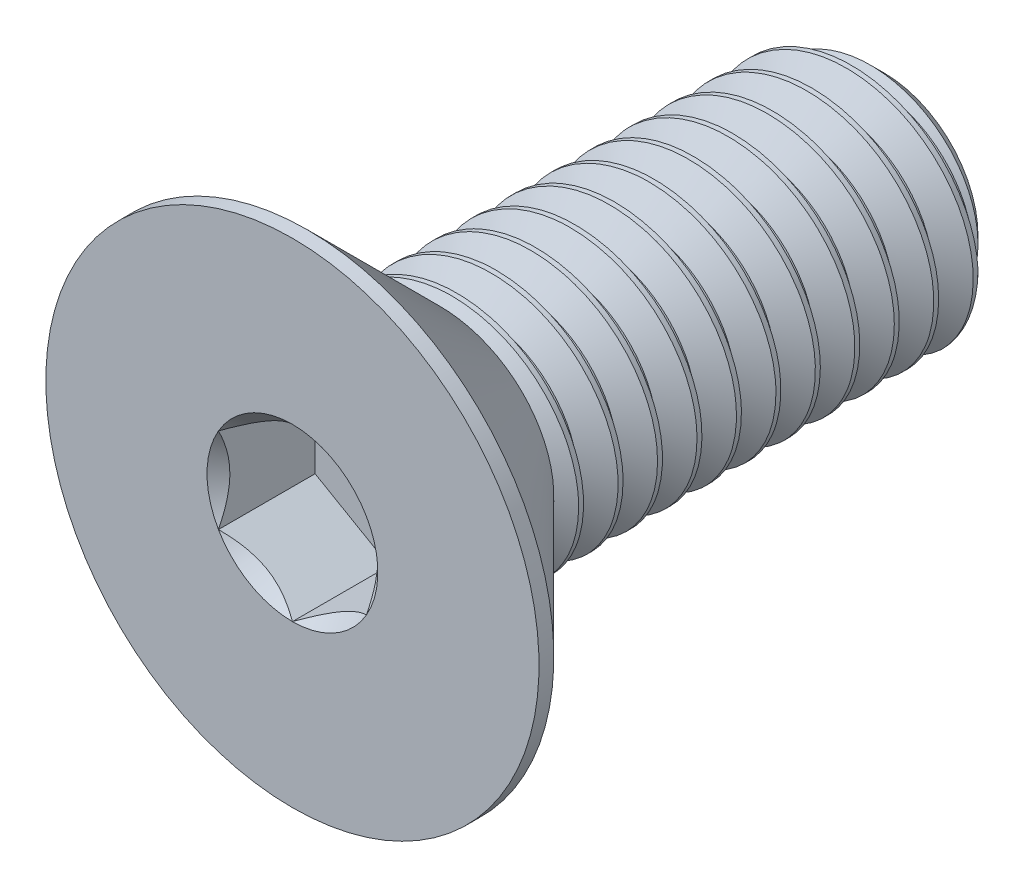
SolidWorks part; units mm, degrees
ref_plane "Front" through (0, 0, 0) normal (0, 0, 1) x (1, 0, 0)
ref_plane "Top" through (0, 0, 0) normal (0, 1, 0) x (1, 0, 0)
ref_plane "Right" through (0, 0, 0) normal (1, 0, 0) x (0, 0, -1)
sketch "Body Sketch" plane through (0, 0, 0) normal (1, 0, 0) x (0, 0, -1)
  line L0 (0, 5) -> (0.3, 5) construction
  line L1 (0.3, 5) -> (2.8, 2.5) construction
  line L2 (0, 2.5) -> (12, 2.5)
  line L3 (12, 2.5) -> (12, 0)
  line L4 (12, 0) -> (0, 0)
  line L5 (0, 0) -> (0, 5) construction
  line L6 (0, 5) -> (0, -5) construction
  line L7 (12, 2.5) -> (12, -2.5) construction
  line L8 (0, -5) -> (0.3, -5) construction
  line L9 (0.3, -5) -> (2.8, -2.5) construction
  line L11 (0, 2.5) -> (0, 0)
  line L12 (2.8, 2.5) -> (2.8, 0) construction
revolve "Body Revolve" add sketch "Body Sketch" angle 360 mid plane about L4
sketch "Sketch3" plane through (0, 0, -12) normal (0, 0, -1) x (-1, 0, 0)
  circle A0 centre (0, 0) radius 2.5
curve "Helix/Spiral1" pitch 0.8 height 12 radius 2.5 centre (0, 0, -12) axis (0, 0, 1) start towards (0, 1, 0)
sketch "Sketch2" plane through (0, 0, 0) normal (1, 0, 0) x (0, 0, -1)
  line L0 (12, 2.5) -> (12.7, 2.5)
  line L1 (12.7, 2.5) -> (12.4, 1.9804)
  line L2 (12.4, 1.9804) -> (12.3, 1.9804)
  line L3 (12.3, 1.9804) -> (12, 2.5)
  line L4 (12.15, 2.2402) -> (12.55, 2.2402) construction
  dimension "D1" = 60
  dimension "D2" = 0.1
  dimension "D3" = 0.4
chamfer "Chamfer1" distance 0.6 angle 45 1 edges at (0, 2.5, -12)
sweep "Cut-Sweep1" cut profiles "Sketch2" path "Helix/Spiral1" align with end faces yes
sketch "Sketch7" plane through (0, 0, 0) normal (1, 0, 0) x (0, 0, -1)
  line L0 (0, 5) -> (0.3, 5) construction
  line L1 (0.3, 5) -> (2.8, 2.5) construction
  line L2 (0, 5) -> (0.3, 5)
  line L3 (0.3, 5) -> (2.8, 2.5)
  line L4 (2.8, 2.5) -> (2.8, 0) construction
  line L5 (2.8, 2.5) -> (2.8, 0)
  line L7 (0, 0) -> (0, 5) construction
  line L8 (0, 0) -> (0, 5)
  line L9 (0, 0) -> (2.8, 0)
  line L10 (5.5, 0) -> (-5.5, 0) construction
revolve "Revolve2" add sketch "Sketch7" angle 360 mid plane about L9
ref_plane "Plane1" through (0, 0, -2.8) normal (0, 0, 1) x (1, 0, 0)
sketch "Sketch8" plane through (0, 0, -2.8) normal (0, 0, 1) x (1, 0, 0)
  circle A0 centre (0, 0) radius 2.5
extrude "Boss-Extrude1" add sketch "Sketch8" against normal through all draft 45
sketch "Sketch5" plane through (0, 0, 0) normal (0, 0, 1) x (1, 0, 0)
  line L1 (1.5, -0.866) -> (1.5, 0.866)
  line L2 (1.5, 0.866) -> (0, 1.7321)
  line L3 (0, 1.7321) -> (-1.5, 0.866)
  line L4 (-1.5, 0.866) -> (-1.5, -0.866)
  line L5 (-1.5, -0.866) -> (0, -1.7321)
  line L6 (0, -1.7321) -> (1.5, -0.866)
  circle A0 centre (0, 0) radius 1.5 construction
  dimension "Hex" = 3
extrude "Cut-Extrude2" cut sketch "Sketch5" against normal blind 1.96
sketch "Sketch6" plane through (0, 0, 0) normal (0, 0, 1) x (1, 0, 0)
  circle A0 centre (0, 0) radius 1.7321
extrude "Cut-Extrude3" cut sketch "Sketch6" against normal blind 1.96 draft 45
equation "\"D3@Helix/Spiral1\" = \"Length@Body Sketch\""
equation "\"D2@Sketch2\" = \"D4@Helix/Spiral1\" * .125"
equation "\"D3@Sketch2\" = \"D4@Helix/Spiral1\" * .5"
equation "\"D1@Chamfer1\" = \"D4@Helix/Spiral1\" * .75"
equation "\"D1@Cut-Extrude2\" = \"Head Ht@Body Sketch\" * .7"
equation "\"D1@Cut-Extrude3\" = \"D1@Cut-Extrude2\""
